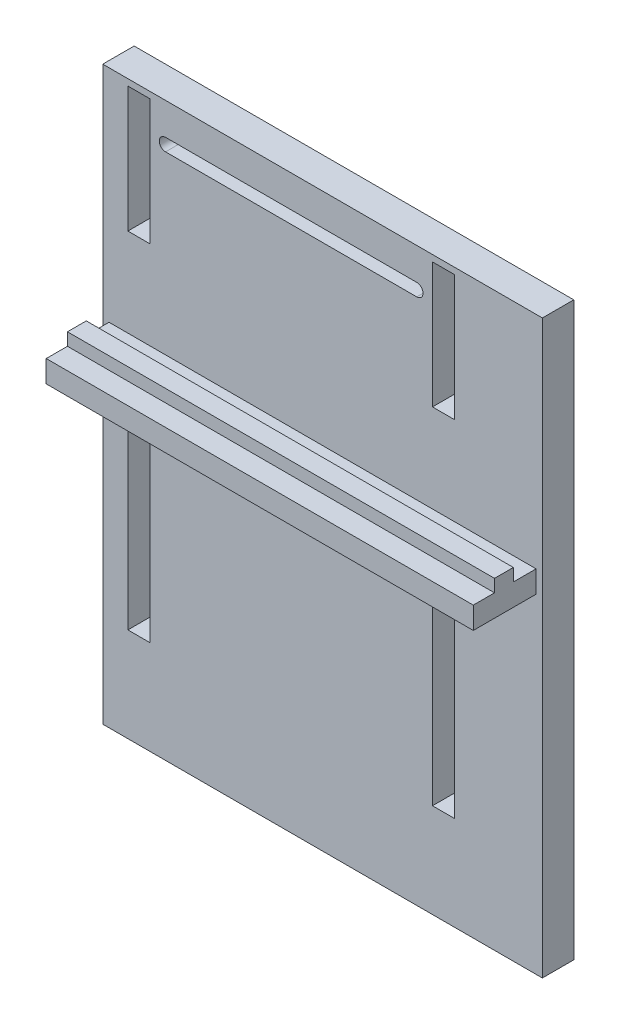
SolidWorks part; units mm, degrees
ref_plane "Front Plane" through (0, 0, 0) normal (0, 0, 1) x (1, 0, 0)
ref_plane "Top Plane" through (0, 0, 0) normal (0, 1, 0) x (1, 0, 0)
ref_plane "Right Plane" through (0, 0, 0) normal (1, 0, 0) x (0, 0, -1)
sketch "Sketch1" plane through (0, 0, 0) normal (0, 0, 1) x (1, 0, 0)
  line L0 (0, 0) -> (0, -50) construction
  line L1 (30, 50) -> (-30, 50)
  line L2 (30, 50) -> (30, -50)
  line L3 (30, -50) -> (-30, -50)
  line L4 (-30, 50) -> (-30, -50)
  line L5 (30, 50) -> (-30, -50) construction
  line L6 (30, -50) -> (-30, 50) construction
  line L7 (26, -5) -> (22.5, -5)
  line L8 (26, -5) -> (26, -35)
  line L9 (26, -35) -> (22.5, -35)
  line L10 (22.5, -5) -> (22.5, -35)
  line L11 (26, -5) -> (22.5, -35) construction
  line L12 (26, -35) -> (22.5, -5) construction
  line L13 (-26, -35) -> (-22.5, -5) construction
  line L14 (-26, -5) -> (-22.5, -35) construction
  line L15 (-22.5, -5) -> (-22.5, -35)
  line L16 (-26, -35) -> (-22.5, -35)
  line L17 (-26, -5) -> (-26, -35)
  line L18 (-26, -5) -> (-22.5, -5)
  line L19 (-26, 20) -> (-22.5, 40) construction
  line L20 (26, 40) -> (22.5, 40)
  line L21 (26, 40) -> (26, 20)
  line L22 (26, 20) -> (22.5, 20)
  line L23 (22.5, 40) -> (22.5, 20)
  line L24 (26, 40) -> (22.5, 20) construction
  line L25 (26, 20) -> (22.5, 40) construction
  line L26 (-26, 40) -> (-22.5, 20) construction
  line L27 (-22.5, 40) -> (-22.5, 20)
  line L28 (-26, 20) -> (-22.5, 20)
  line L29 (-26, 40) -> (-26, 20)
  line L30 (-26, 40) -> (-22.5, 40)
  point P0 (0, 0)
  point P6 (24.25, -20)
  point P17 (-24.25, -20)
  point P22 (24.25, 30)
  point P27 (-24.25, 30)
  dimension "D1" = 100
  dimension "D2" = 60
  dimension "D3" = 15
  dimension "D4" = 30
  dimension "D5" = 3.5
  dimension "D6" = 4
  dimension "D7" = 20
  dimension "D8" = 3.5
  dimension "D9" = 10
extrude "Boss-Extrude1" add sketch "Sketch1" along normal blind 5
sketch "Sketch2" plane through (0, 0, 5) normal (0, 0, 1) x (1, 0, 0)
  line L0 (30, -50) -> (30, 50) construction
  line L1 (29, 5.924) -> (-29, 5.924)
  line L2 (29, 5.924) -> (29, 2.424)
  line L3 (29, 2.424) -> (-29, 2.424)
  line L4 (-29, 5.924) -> (-29, 2.424)
  line L5 (29, 5.924) -> (-29, 2.424) construction
  line L6 (29, 2.424) -> (-29, 5.924) construction
  line L7 (-30, 50) -> (-30, -50) construction
  point P4 (0, 4.174)
  point P5 (29, 4.174)
  point P8 (30, 0)
  dimension "D1" = 3.5
  dimension "D2" = 1
  dimension "D3" = 4.174
  dimension "D4" = 1
extrude "Boss-Extrude2" add sketch "Sketch2" along normal blind 10
sketch "Sketch3" plane through (0, 5.924, 0) normal (0, 1, 0) x (1, 0, 0)
  line L0 (-26, -8.6213) -> (26, -8.6213)
  line L1 (-26, -8.6213) -> (-26, -11.6213)
  line L2 (26, -8.6213) -> (26, -11.6213)
  line L3 (-26, -11.6213) -> (26, -11.6213)
  line L4 (-26, -8.6213) -> (26, -11.6213) construction
  line L5 (26, -8.6213) -> (-26, -11.6213) construction
  point P1 (0, -10.1213)
  dimension "D1" = 3
extrude "Boss-Extrude3" add sketch "Sketch3" along normal blind 2
sketch "Sketch4" plane through (0, 0, 0) normal (0, 0, -1) x (-1, 0, 0)
  line L0 (-15, 0) -> (15, 0) construction
  circle A0 centre (15, 0) radius 2
  circle A1 centre (-15, 0) radius 2
  point P4 (0, 0)
  dimension "D1" = 4
  dimension "D2" = 4
  dimension "D3" = 30
extrude "Boss-Extrude4" add sketch "Sketch4" along normal blind 20
sketch "Sketch5" plane through (0, 0, 5) normal (0, 0, 1) x (1, 0, 0)
  line L0 (0, 5.924) -> (0, 34.924) construction
  line L1 (-26, 5.924) -> (26, 5.924) construction
  line L2 (-20, 34.924) -> (20, 34.924) construction
  line L3 (-20, 35.924) -> (20, 35.924)
  line L4 (-20, 33.924) -> (20, 33.924)
  arc A0 (-20, 35.924) -> (-20, 33.924) centre (-20, 34.924) ccw
  arc A1 (20, 33.924) -> (20, 35.924) centre (20, 34.924) ccw
  point P7 (0, 34.924)
  dimension "D2" = 1
  dimension "D1" = 29
  dimension "D3" = 40
extrude "Cut-Extrude1" cut sketch "Sketch5" against normal through all
ref_axis "Axis1" through (15, 0, -20) along (0, 0, 1)
ref_plane "Plane1" through (15, 0, 0) normal (1, 0, 0) x (0, 0, -1)
ref_plane "Plane2" through (26.33, 0, 0) normal (1, 0, 0) x (0, 0, -1)
sketch "Sketch6" plane through (26, 0, 0) normal (1, 0, 0) x (0, 0, -1)
  line L4 (-11.6213, 5.924) -> (-8.6213, 5.924)
  line L5 (-8.6213, 5.924) -> (-8.6213, 7.924)
  line L6 (-8.6213, 7.924) -> (-11.6213, 7.924)
  line L7 (-11.6213, 7.924) -> (-11.6213, 5.924)
  line L8 (-11.6213, 5.924) -> (-8.6213, 5.924)
  line L9 (-8.6213, 5.924) -> (-8.6213, 7.924)
  line L10 (-8.6213, 7.924) -> (-11.6213, 7.924)
  line L11 (-11.6213, 7.924) -> (-11.6213, 5.924)
  dimension "D1" = 0
extrude "Boss-Extrude5" add sketch "Sketch6" along normal up to surface (3 mm away) up to face at (29, 4.174, 10)
sketch "Sketch7" plane through (-26, 0, 0) normal (-1, 0, 0) x (0, 0, 1)
  line L4 (8.6213, 5.924) -> (11.6213, 5.924)
  line L5 (11.6213, 5.924) -> (11.6213, 7.924)
  line L6 (11.6213, 7.924) -> (8.6213, 7.924)
  line L7 (8.6213, 7.924) -> (8.6213, 5.924)
  line L8 (8.6213, 5.924) -> (11.6213, 5.924)
  line L9 (11.6213, 5.924) -> (11.6213, 7.924)
  line L10 (11.6213, 7.924) -> (8.6213, 7.924)
  line L11 (8.6213, 7.924) -> (8.6213, 5.924)
  dimension "D1" = 0
extrude "Boss-Extrude6" add sketch "Sketch7" along normal up to surface (3 mm away) up to face at (-29, 4.174, 10)
ref_plane "Plane3" through (0, 0, 10.1213) normal (0, 0, 1) x (1, 0, 0)
ref_plane "Plane4" through (0, 5.924, 0) normal (0, 1, 0) x (1, 0, 0)
ref_axis "Axis2" through (26.33, 5.924, -22.5107) along (0, 0, 1)
ref_axis "Axis3" through (31.9, 5.924, 10.1213) along (-1, 0, 0)
ref_axis "Axis4" through (26.33, 5.824, 10.1213) along (0, 1, 0)
ref_point "Point1"
sketch "Sketch8" plane through (30, 0, 0) normal (1, 0, 0) x (0, 0, -1)
  line L4 (0, -50) -> (0, 50)
  line L5 (0, 50) -> (-5, 50)
  line L6 (-5, 50) -> (-5, -50)
  line L7 (-5, -50) -> (0, -50)
  line L8 (0, -50) -> (0, 50)
  line L9 (0, 50) -> (-5, 50)
  line L10 (-5, 50) -> (-5, -50)
  line L11 (-5, -50) -> (0, -50)
  dimension "D1" = 0
extrude "Boss-Extrude7" add sketch "Sketch8" along normal blind 10
sketch "Sketch9" plane through (29, 0, 0) normal (1, 0, 0) x (0, 0, -1)
  line L8 (-5, 2.424) -> (-5, 5.924)
  line L9 (-5, 5.924) -> (-8.6213, 5.924)
  line L10 (-8.6213, 5.924) -> (-8.6213, 7.924)
  line L11 (-8.6213, 7.924) -> (-11.6213, 7.924)
  line L12 (-11.6213, 7.924) -> (-11.6213, 5.924)
  line L13 (-11.6213, 5.924) -> (-15, 5.924)
  line L14 (-15, 5.924) -> (-15, 2.424)
  line L15 (-15, 2.424) -> (-5, 2.424)
  line L16 (-5, 2.424) -> (-5, 5.924)
  line L17 (-5, 5.924) -> (-8.6213, 5.924)
  line L18 (-8.6213, 5.924) -> (-8.6213, 7.924)
  line L19 (-8.6213, 7.924) -> (-11.6213, 7.924)
  line L20 (-11.6213, 7.924) -> (-11.6213, 5.924)
  line L21 (-11.6213, 5.924) -> (-15, 5.924)
  line L22 (-15, 5.924) -> (-15, 2.424)
  line L23 (-15, 2.424) -> (-5, 2.424)
  dimension "D1" = 0
extrude "Boss-Extrude8" add sketch "Sketch9" along normal blind 10
sketch "Sketch11" plane through (0, 0, 5) normal (0, 0, 1) x (1, 0, 0)
  line L0 (-30, 50) -> (-30, -50) construction
  line L1 (40, 50) -> (-30, 50)
  line L2 (40, 50) -> (40, 41.0197)
  line L3 (40, 41.0197) -> (-30, 41.0197)
  line L4 (-30, 50) -> (-30, 41.0197)
  line L5 (40, 50) -> (-30, 41.0197) construction
  line L6 (40, 41.0197) -> (-30, 50) construction
  point P4 (5, 45.5099)
extrude "Cut-Extrude2" cut sketch "Sketch11" against normal through all
